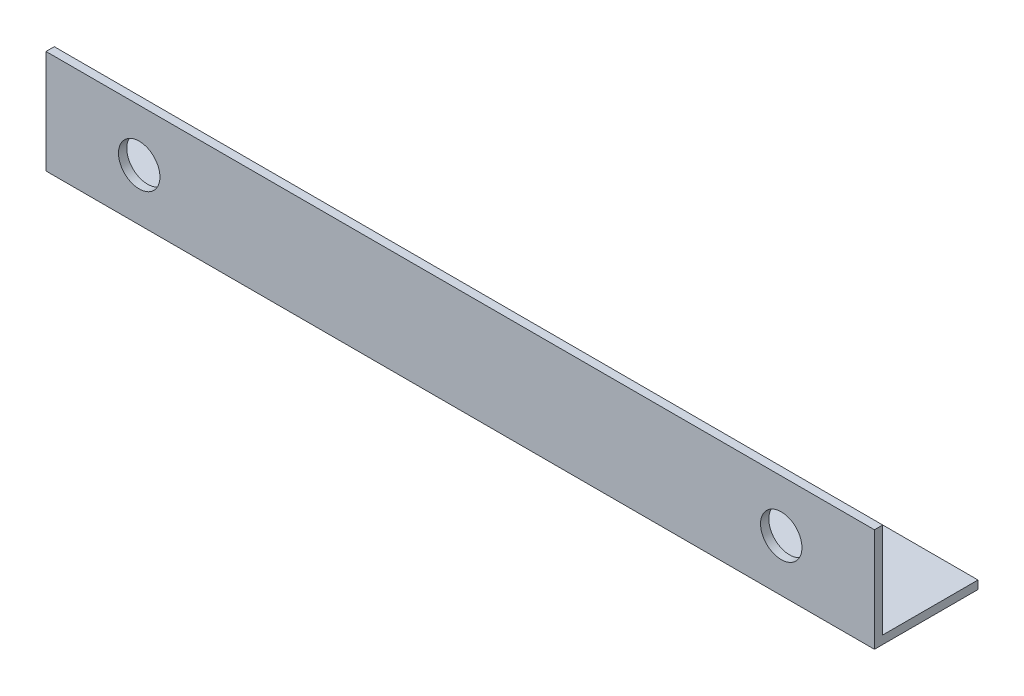
SolidWorks part; units mm, degrees
ref_plane "Спереди" through (0, 0, 0) normal (0, 0, 1) x (1, 0, 0)
ref_plane "Сверху" through (0, 0, 0) normal (0, 1, 0) x (1, 0, 0)
ref_plane "Справа" through (0, 0, 0) normal (1, 0, 0) x (0, 0, -1)
sketch "Эскиз1" plane through (0, 0, 0) normal (1, 0, 0) x (0, 0, -1)
  line L0 (0, 25) -> (0, 0)
  line L1 (0, 0) -> (25, 0)
extrude "Вытянуть-Тонкостенный1" add sketch "Эскиз1" along normal blind 200 thin thin type one direction reverse wall 2
sketch "Эскиз2" plane through (0, 0, 0) normal (0, 0, 1) x (1, 0, 0)
  line L0 (100, 0) -> (100, -9.5468) construction
  line L1 (200, 0) -> (0, 0) construction
  circle A0 centre (22.5, 12.5) radius 5
  circle A1 centre (177.5, 12.5) radius 5
  dimension "D1" = 77.5
extrude "Вырез-Вытянуть1" cut sketch "Эскиз2" against normal through all
